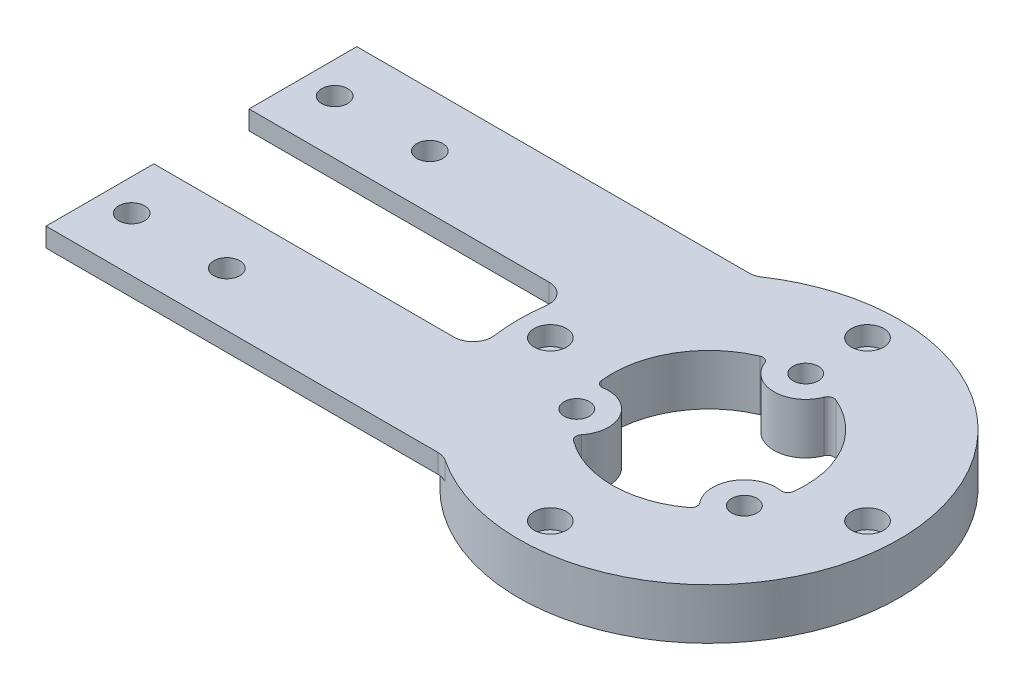
SolidWorks part; units mm, degrees
ref_plane "Front Plane" through (0, 0, 0) normal (0, 0, 1) x (1, 0, 0)
ref_plane "Top Plane" through (0, 0, 0) normal (0, 1, 0) x (1, 0, 0)
ref_plane "Right Plane" through (0, 0, 0) normal (1, 0, 0) x (0, 0, -1)
sketch "Sketch1" plane through (0, 0, 0) normal (0, 1, 0) x (1, 0, 0)
  circle A0 centre (0, 0) radius 30
  circle A1 centre (0, 0) radius 10
  circle A2 centre (0, 0) radius 15.25 construction
  circle A3 centre (0, 15.25) radius 2
  circle A4 centre (13.2069, -7.625) radius 2
  circle A5 centre (-13.2069, -7.625) radius 2
  circle A6 centre (0, 0) radius 25 construction
  circle A7 centre (0, 25) radius 2.55
  circle A8 centre (25, 0) radius 2.55
  circle A9 centre (0, -25) radius 2.55
  circle A10 centre (-25, 0) radius 2.55
  point P13 (0, 0)
  point P24 (0, 0)
  dimension "D1" = 30.5
  dimension "D2" = 60
  dimension "D3" = 20
  dimension "D4" = 4
  dimension "D6" = 5.1
  dimension "D7" = 50
  dimension "D5" = 3
  dimension "D8" = 4
extrude "Boss-Extrude1" add sketch "Sketch1" along normal blind 3
sketch "Sketch2" plane through (0, 3, 0) normal (0, 1, 0) x (1, 0, 0)
  line L1 (-80, 24.5) -> (-17, 24.5)
  line L2 (-80, 24.5) -> (-80, 7.5)
  line L3 (-80, 7.5) -> (-17, 7.5)
  line L4 (-17, 24.5) -> (-17, 7.5)
  line L5 (-80, -7.5) -> (-17, -7.5)
  line L6 (-80, -7.5) -> (-80, -24.5)
  line L7 (-80, -24.5) -> (-17, -24.5)
  line L8 (-17, -7.5) -> (-17, -24.5)
  circle A0 centre (0, 0) radius 10 construction
  dimension "D1" = 17
  dimension "D2" = 15
  dimension "D3" = 7.5
  dimension "D4" = 17
  dimension "D5" = 80
extrude "Boss-Extrude2" add sketch "Sketch2" against normal up to surface (3 mm away) up to face at (0, 0, 30)
sketch "Sketch3" plane through (0, 0, 0) normal (0, -1, 0) x (1, 0, 0)
  circle A0 centre (0, 0) radius 30
  arc A1 (-17.3133, -24.5) -> (-17.3133, 24.5) centre (0, 0) ccw construction
  circle A2 centre (0, -15.25) radius 2 construction
  circle A3 centre (13.2069, 7.625) radius 2 construction
  circle A4 centre (-13.2069, 7.625) radius 2 construction
  circle A5 centre (0, 0) radius 10 construction
  circle A6 centre (0, -15.25) radius 2
  circle A7 centre (13.2069, 7.625) radius 2
  circle A8 centre (-13.2069, 7.625) radius 2
  circle A9 centre (0, 0) radius 10
extrude "Boss-Extrude3" add sketch "Sketch3" along normal blind 5
sketch "Sketch4" plane through (0, 0, 0) normal (0, -1, 0) x (1, 0, 0)
  line L0 (-80, 24.5) -> (-80, 7.5) construction
  line L1 (-80, 7.5) -> (-29.0474, 7.5) construction
  line L2 (-80, -24.5) -> (-17.3133, -24.5) construction
  circle A0 centre (-75, 16) radius 2.05
  circle A1 centre (-60, 16) radius 2.05
  circle A2 centre (-75, -16) radius 2.05
  circle A3 centre (-60, -16) radius 2.05
  dimension "D1" = 4.1
  dimension "D2" = 5
  dimension "D3" = 15
  dimension "D4" = 8.5
  dimension "D5" = 8.5
extrude "Cut-Extrude1" cut sketch "Sketch4" against normal through all
fillet "Fillet1" radius 3 4 edges at (-17.3133, 1.5, -24.5) (-29.0474, 1.5, -7.5) (-29.0474, 1.5, 7.5) (-17.3133, 1.5, 24.5)
sketch "Sketch5" plane through (0, 3, 0) normal (0, 1, 0) x (1, 0, 0)
  arc A0 (-4.9324, 14.4303) -> (4.9324, 14.4303) centre (0, 15.25) ccw
  arc A1 (14.9632, -2.9436) -> (10.0309, -11.4867) centre (13.2069, -7.625) ccw
  arc A2 (-10.0309, -11.4867) -> (-14.9632, -2.9436) centre (-13.2069, -7.625) ccw
  arc A3 (-4.9324, 14.4303) -> (-14.9632, -2.9436) centre (0, 0) ccw
  circle A4 centre (0, 15.25) radius 2 construction
  arc A5 (-10.0309, -11.4867) -> (10.0309, -11.4867) centre (0, 0) ccw
  arc A6 (14.9632, -2.9436) -> (4.9324, 14.4303) centre (0, 0) ccw
  dimension "D1" = 3
extrude "Cut-Extrude2" cut sketch "Sketch5" against normal through all
fillet "Fillet2" radius 1 6 edges at (10.0309, -1, 11.4867) (-10.0309, -1, 11.4867) (-14.9632, -1, 2.9436) (14.9632, -1, 2.9436) (4.9324, -1, -14.4303) (-4.9324, -1, -14.4303)
